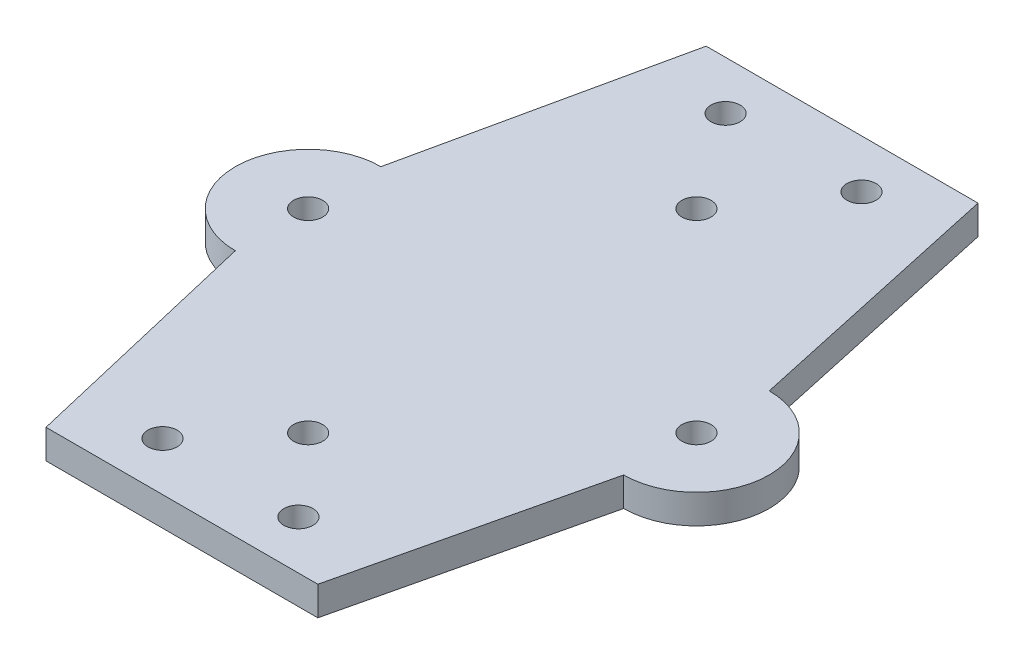
SolidWorks part; units mm, degrees
ref_plane "Front Plane" through (0, 0, 0) normal (0, 0, 1) x (1, 0, 0)
ref_plane "Top Plane" through (0, 0, 0) normal (0, 1, 0) x (1, 0, 0)
ref_plane "Right Plane" through (0, 0, 0) normal (1, 0, 0) x (0, 0, -1)
sketch "Sketch1" plane through (0, 0, 0) normal (0, 1, 0) x (1, 0, 0)
  line L0 (-20, 7.5) -> (-14, 35)
  line L1 (-14, 35) -> (14, 35)
  line L2 (0, 35) -> (0, -33)
  line L3 (14, -33) -> (-14, -33)
  line L4 (-14, -33) -> (-20, -7.5)
  line L5 (14, -33) -> (20, -7.5)
  line L6 (20, 7.5) -> (14, 35)
  circle A0 centre (-20, 0) radius 1.5
  circle A1 centre (-20, 0) radius 7.5
  circle A2 centre (-7, 30) radius 1.5
  circle A3 centre (-7, -28) radius 1.5
  circle A4 centre (7, -28) radius 1.5
  circle A5 centre (7, 30) radius 1.5
  circle A6 centre (20, 0) radius 1.5
  circle A7 centre (20, 0) radius 7.5
  circle A8 centre (0, 20) radius 1.5
  circle A9 centre (0, -20) radius 1.5
  dimension "D2" = 15
  dimension "D3" = 3
  dimension "D10" = 3
  dimension "D12" = 3
  dimension "D1" = 68
  dimension "D4" = 20
  dimension "D5" = 7
  dimension "D6" = 30
  dimension "D7" = 28
  dimension "D8" = 14
  dimension "D9" = 35
  dimension "D11" = 20
  dimension "D13" = 20
extrude "Boss-Extrude1" add sketch "Sketch1" along normal blind 1.5 and the other way blind 1.5 contours A1 L4 L3 L2 L1 L0 A3 A2 | L5 A7 L6 L1 L2 L3 A4 A5 | A7 A6 | A1 A0 region at (-8.3822, 0, -0.9976) region at (-14.8467, 0, -5.1533) region at (8.3822, 0, -0.9976) region at (25.1533, 0, -5.1533)
